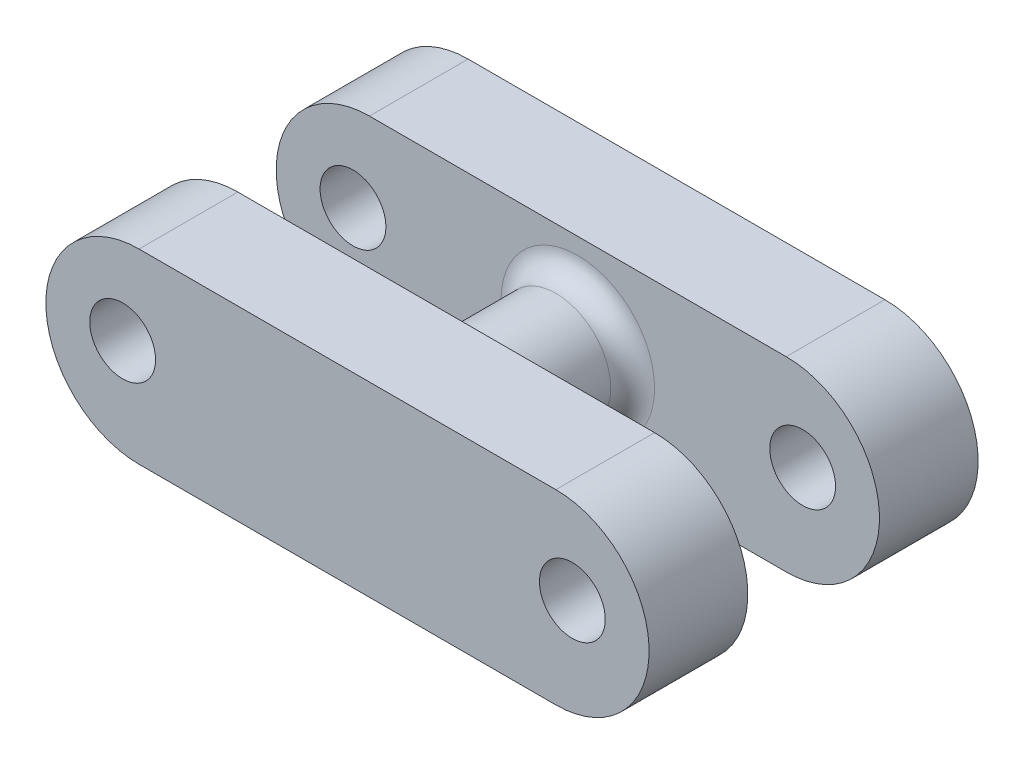
SolidWorks part; units mm, degrees
material "1.0044 (S275JR)"
ref_plane "Płaszczyzna przednia" through (0, 0, 0) normal (0, 0, 1) x (1, 0, 0)
ref_plane "Płaszczyzna górna" through (0, 0, 0) normal (0, 1, 0) x (1, 0, 0)
ref_plane "Płaszczyzna prawa" through (0, 0, 0) normal (1, 0, 0) x (0, 0, -1)
sketch "Szkic1" plane through (0, 0, 0) normal (0, 0, 1) x (1, 0, 0)
  line L0 (0, 0) -> (0, 17)
  line L2 (55, 17) -> (55, 0)
  line L3 (55, 0) -> (10, 0)
  line L5 (0, 17) -> (55, 17)
  line L7 (10, 0) -> (0, 0)
  line L8 (7, 9) -> (48, 9) construction
  circle A0 centre (48, 9) radius 3
  circle A1 centre (7, 9) radius 3
  point P18 (55, 0)
  point P21 (0, 0)
  point P28 (55, 17)
  dimension "D1" = 6
  dimension "D2" = 6
  dimension "D9" = 55
  dimension "D3" = 41
  dimension "D4" = 7
  dimension "D5" = 8
  dimension "D8" = 9
  dimension "D11" = 10
extrude "Dodanie-wyciągnięcie1" add sketch "Szkic1" along normal blind 30
sketch "Szkic2" plane through (55, 0, 0) normal (1, 0, 0) x (0, 0, -1)
  line L0 (-30, 0) -> (0, 0) construction
  line L1 (-21, 0) -> (-9, 0)
  line L2 (-21, 0) -> (-21, 17)
  line L3 (-21, 17) -> (-9, 17)
  line L4 (-9, 0) -> (-9, 17)
  line L5 (0, 0) -> (0, 17) construction
  line L6 (-30, 0) -> (-30, 17) construction
  line L8 (-30, 17) -> (0, 17) construction
  dimension "D1" = 9
  dimension "D2" = 9
extrude "Wytnij-wyciągnięcie1" cut sketch "Szkic2" against normal through all
sketch "Szkic3" plane through (0, 0, 0) normal (0, 0, -1) x (-1, 0, 0)
  line L1 (-55, 0) -> (-55, 17) construction
  line L2 (-55, 17) -> (0, 17) construction
  circle A0 centre (-27.5, 8.5) radius 5
  point P7 (-55, 8.5)
  point P9 (-27.5, 17)
  dimension "D1" = 10
extrude "Dodanie-wyciągnięcie2" add sketch "Szkic3" against normal up to surface (30 mm away) up to face at (27.5, 8.5, 30)
fillet "Zaokrąglenie3" radius 2 2 edges at (22.5, 8.5, 9) (32.5, 8.5, 21)
fillet "Zaokrąglenie6" 2 edges at (55, 17, 4.5) (55, 0, 4.5) type full round first side face at (27.5, 17, 4.5) second side face at (27.5, 0, 4.5) middle face at (55, 8.5, 4.5)
fillet "Zaokrąglenie7" 2 edges at (55, 17, 25.5) (55, 0, 25.5) type full round first side face at (27.5, 17, 25.5) second side face at (27.5, 0, 25.5) middle face at (55, 8.5, 25.5)
fillet "Zaokrąglenie8" 2 edges at (0, 17, 4.5) (0, 0, 4.5) type full round first side face at (23.25, 17, 4.5) second side face at (23.25, 0, 4.5) middle face at (0, 8.5, 4.5)
fillet "Zaokrąglenie9" 2 edges at (0, 17, 25.5) (0, 0, 25.5) type full round first side face at (23.25, 17, 25.5) second side face at (23.25, 0, 25.5) middle face at (0, 8.5, 25.5)
